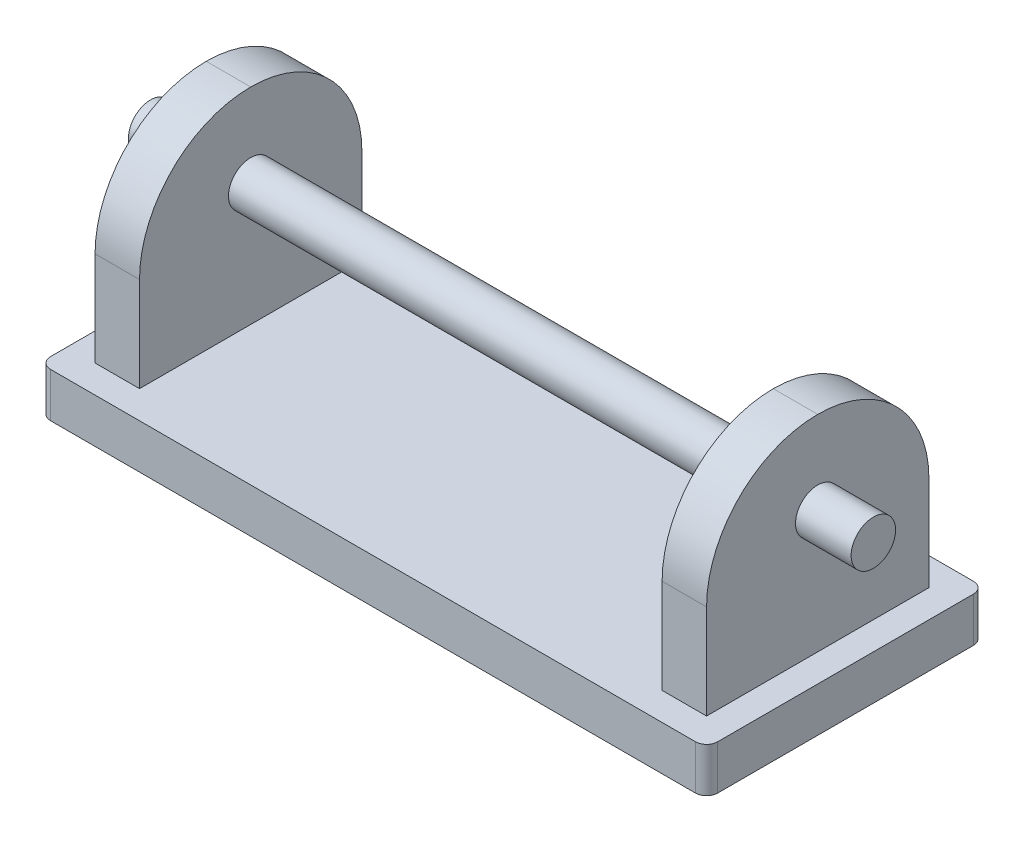
SolidWorks part; units mm, degrees
ref_plane "Front Plane" through (0, 0, 0) normal (0, 0, 1) x (1, 0, 0)
ref_plane "Top Plane" through (0, 0, 0) normal (0, 1, 0) x (1, 0, 0)
ref_plane "Right Plane" through (0, 0, 0) normal (1, 0, 0) x (0, 0, -1)
sketch "Sketch1" plane through (0, 0, 0) normal (0, 1, 0) x (1, 0, 0)
  line L1 (60, -25) -> (-60, -25)
  line L2 (60, -25) -> (60, 25)
  line L3 (60, 25) -> (-60, 25)
  line L4 (-60, -25) -> (-60, 25)
  line L5 (60, -25) -> (-60, 25) construction
  line L6 (60, 25) -> (-60, -25) construction
  point P0 (0, 0)
  dimension "D1" = 120
  dimension "D2" = 50
extrude "Boss-Extrude1" add sketch "Sketch1" along normal blind 8
sketch "Sketch2" plane through (0, 8, 0) normal (0, 1, 0) x (1, 0, 0)
  line L0 (60, 25) -> (-60, 25) construction
  line L1 (-55, 20) -> (-47, 20)
  line L2 (-55, 20) -> (-55, -20)
  line L3 (-55, -20) -> (-47, -20)
  line L4 (-47, 20) -> (-47, -20)
  line L5 (-55, 20) -> (-47, -20) construction
  line L6 (-55, -20) -> (-47, 20) construction
  line L7 (47, 20) -> (55, 20)
  line L8 (47, 20) -> (47, -20)
  line L9 (47, -20) -> (55, -20)
  line L10 (55, 20) -> (55, -20)
  line L11 (47, 20) -> (55, -20) construction
  line L12 (47, -20) -> (55, 20) construction
  line L13 (-60, 25) -> (-60, -25) construction
  line L14 (60, -25) -> (60, 25) construction
  point P0 (-51, 0)
  point P5 (51, 0)
  dimension "D1" = 8
  dimension "D2" = 8
  dimension "D3" = 40
  dimension "D4" = 40
  dimension "D5" = 5
  dimension "D6" = 5
  dimension "D7" = 5
  dimension "D8" = 5
extrude "Boss-Extrude2" add sketch "Sketch2" along normal blind 37
fillet "Fillet1" radius 20 4 edges at (51, 45, -20) (51, 45, 20) (-51, 45, -20) (-51, 45, 20)
sketch "Sketch3" plane through (-55, 0, 0) normal (-1, 0, 0) x (0, 0, 1)
  line L0 (-20, 8) -> (20, 8) construction
  line L1 (20, 25) -> (20, 8) construction
  circle A0 centre (0, 30) radius 4
  dimension "D1" = 8
  dimension "D2" = 22
  dimension "D3" = 20
extrude "Boss-Extrude3" add sketch "Sketch3" along normal blind 10 and the other way blind 120
fillet "Fillet2" radius 2 4 edges at (-60, 4, 25) (-60, 4, -25) (60, 4, -25) (60, 4, 25)
